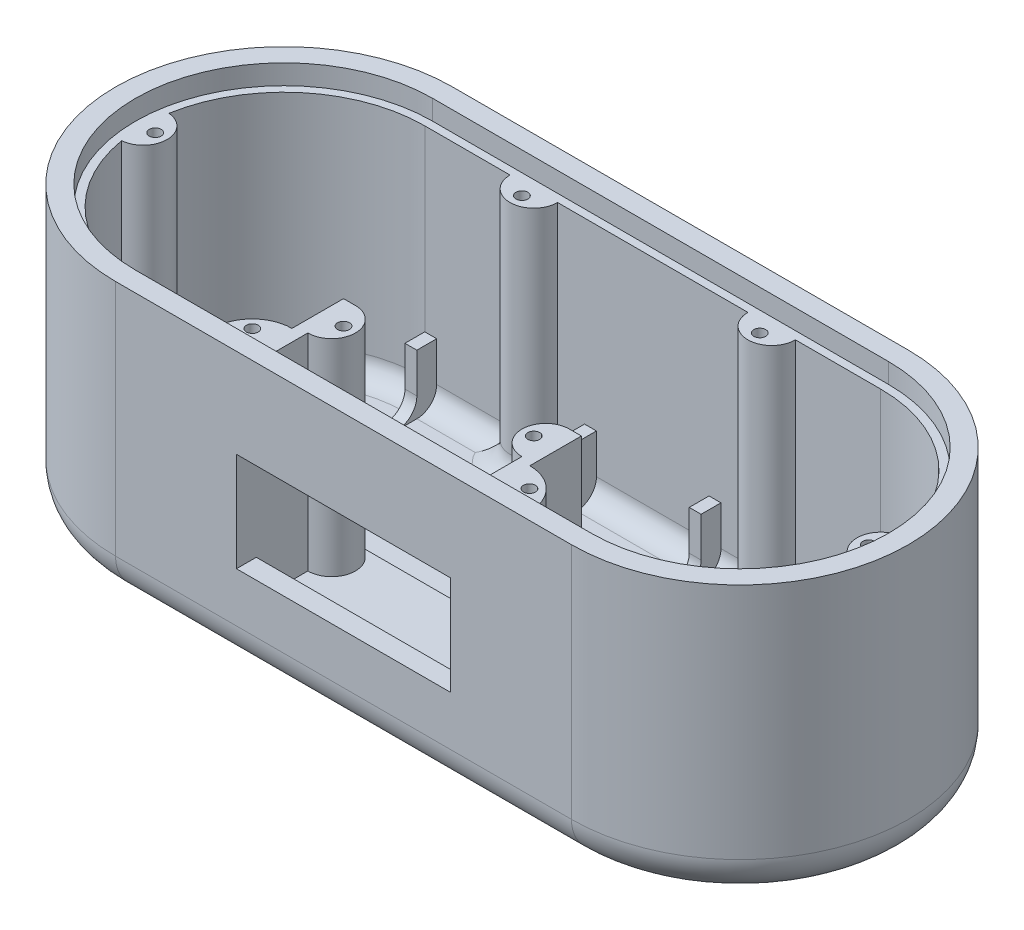
SolidWorks part; units mm, degrees
ref_plane "Front Plane" through (0, 0, 0) normal (0, 0, 1) x (1, 0, 0)
ref_plane "Top Plane" through (0, 0, 0) normal (0, 1, 0) x (1, 0, 0)
ref_plane "Right Plane" through (0, 0, 0) normal (1, 0, 0) x (0, 0, -1)
sketch "Sketch1" plane through (0, 0, 0) normal (0, 1, 0) x (1, 0, 0)
  line L0 (-57.5, 0) -> (57.5, 0) construction
  line L1 (-57.5, 42.5) -> (57.5, 42.5)
  line L2 (-57.5, -42.5) -> (57.5, -42.5)
  line L3 (-57.5, 0) -> (-100, 0) construction
  line L4 (57.5, 0) -> (100, 0) construction
  arc A0 (-57.5, 42.5) -> (-57.5, -42.5) centre (-57.5, 0) ccw
  arc A1 (57.5, -42.5) -> (57.5, 42.5) centre (57.5, 0) ccw
  point P3 (0, 0)
  point P12 (31.5337, 0)
  point P13 (0, 0)
  dimension "D1" = 85
  dimension "D2" = 200
extrude "Boss-Extrude1" add sketch "Sketch1" along normal blind 70
fillet "Fillet1" radius 10 4 edges at (0, 0, 42.5) (100, 0, 0) (0, 0, -42.5) (-100, 0, 0)
sketch "Sketch2" plane through (0, 70, 0) normal (0, 1, 0) x (1, 0, 0)
  line L2 (-57.5, -37.5) -> (-30, -37.5)
  line L3 (-30, -37.5) -> (-30, -12.5)
  line L4 (-57.5, -37.5) -> (57.5, -37.5)
  line L5 (57.5, 37.5) -> (-57.5, 37.5)
  line L7 (57.5, 37.5) -> (-57.5, 37.5)
  line L8 (-30, -12.5) -> (30, -12.5)
  line L9 (30, -12.5) -> (30, -37.5)
  line L10 (30, -37.5) -> (57.5, -37.5)
  line L11 (0, -12.5) -> (0, 0) construction
  arc A4 (-57.5, 37.5) -> (-57.5, -37.5) centre (-57.5, 0) ccw
  arc A5 (57.5, -37.5) -> (57.5, 37.5) centre (57.5, 0) ccw
  arc A6 (-57.5, 37.5) -> (-57.5, -37.5) centre (-57.5, 0) ccw
  arc A7 (57.5, -37.5) -> (57.5, 37.5) centre (57.5, 0) ccw
  dimension "D2" = 25
  dimension "D3" = 60
  dimension "D1" = 5
extrude "Cut-Extrude1" cut sketch "Sketch2" against normal blind 5
sketch "Sketch3" plane through (0, 65, 0) normal (0, 1, 0) x (1, 0, 0)
  line L0 (30, -12.5) -> (30, -37.5) construction
  line L1 (-30, -37.5) -> (-30, -12.5) construction
  line L2 (-30, -25.5) -> (30, -25.5) construction
  line L3 (-40, -35.5) -> (-30, -35.5) construction
  line L4 (40, -35.5) -> (30, -35.5) construction
  line L5 (-37.0711, -28.4289) -> (-30, -35.5) construction
  line L6 (-30, -37.5) -> (-30, -12.5) construction
  line L7 (30, -35.5) -> (37.0711, -28.4289) construction
  line L8 (-30, 32.5) -> (-30, 35.5) construction
  line L9 (30, 35.5) -> (30, 32.5) construction
  line L10 (-36, 35.5) -> (-57.5, 35.5)
  line L11 (24, 35.5) -> (-24, 35.5)
  line L12 (32, -35.5) -> (57.5, -35.5)
  line L13 (57.5, 35.5) -> (-57.5, 35.5)
  line L14 (-57.5, -35.5) -> (-32, -35.5)
  line L15 (-32, -35.5) -> (-32, -10.5)
  line L16 (-32, -10.5) -> (32, -10.5)
  line L17 (32, -10.5) -> (32, -35.5)
  line L18 (40, -35.5) -> (57.5, -35.5)
  line L19 (57.5, 35.5) -> (36, 35.5)
  line L20 (-57.5, -35.5) -> (-40, -35.5)
  line L21 (93, 0) -> (95, 0) construction
  line L24 (-93, 0) -> (-95, 0) construction
  line L25 (-34.9497, -30.5503) -> (34.9497, -30.5503) construction
  line L26 (-90, 0) -> (-87, 0) construction
  line L27 (90, 0) -> (87, 0) construction
  line L28 (30, 32.5) -> (30, 29.5) construction
  line L29 (-30, 32.5) -> (-30, 29.5) construction
  line L30 (-30, 29.5) -> (-30, -12.5) construction
  line L31 (30, 29.5) -> (30, -12.5) construction
  line L32 (-30, -25.5) -> (-30, -12.5)
  line L33 (-30, -12.5) -> (30, -12.5)
  line L34 (30, -12.5) -> (30, -25.5)
  arc A0 (40, -35.5) -> (30, -25.5) centre (30, -35.5) ccw
  arc A1 (-92.493, 5.9785) -> (-92.493, -5.9785) centre (-93, 0) cw
  arc A2 (-30, -25.5) -> (-40, -35.5) centre (-30, -35.5) ccw
  arc A3 (92.493, 5.9785) -> (92.493, -5.9785) centre (93, 0) ccw
  arc A4 (57.5, -35.5) -> (57.5, 35.5) centre (57.5, 0) ccw
  arc A5 (-57.5, 35.5) -> (-57.5, -35.5) centre (-57.5, 0) ccw
  arc A6 (57.5, -35.5) -> (92.493, -5.9785) centre (57.5, 0) ccw
  arc A7 (-57.5, 35.5) -> (-92.493, 5.9785) centre (-57.5, 0) ccw
  arc A8 (24, 35.5) -> (36, 35.5) centre (30, 35.5) ccw
  arc A9 (-36, 35.5) -> (-24, 35.5) centre (-30, 35.5) ccw
  arc A10 (-92.493, -5.9785) -> (-57.5, -35.5) centre (-57.5, 0) ccw
  arc A11 (92.493, 5.9785) -> (57.5, 35.5) centre (57.5, 0) ccw
  arc A12 (57.5, -37.5) -> (57.5, 37.5) centre (57.5, 0) ccw construction
  arc A13 (-57.5, 37.5) -> (-57.5, -37.5) centre (-57.5, 0) ccw construction
  arc A14 (-92.493, 5.9785) -> (-93, 0) centre (-57.5, 0) ccw construction
  arc A15 (-92.493, -5.9785) -> (-93, 0) centre (-57.5, 0) cw construction
  arc A16 (92.493, 5.9785) -> (93, 0) centre (57.5, 0) cw construction
  arc A17 (92.493, -5.9785) -> (93, 0) centre (57.5, 0) ccw construction
  circle A18 centre (-90, 0) radius 1.5
  circle A19 centre (-30, 32.5) radius 1.5
  circle A20 centre (30, 32.5) radius 1.5
  circle A21 centre (90, 0) radius 1.5
  circle A22 centre (34.9497, -30.5503) radius 1.5
  circle A23 centre (-34.9497, -30.5503) radius 1.5
  dimension "D2" = 10
  dimension "D3" = 6
  dimension "D4" = 3
  dimension "D5" = 3
  dimension "D6" = 42
  dimension "D7" = 3
  dimension "D1" = 2
extrude "Cut-Extrude2" cut sketch "Sketch3" against normal offset from surface (60 mm away) 5 up to face at (0, 0, 0)
fillet "Fillet2" radius 5 18 edges at (-48.75, 5, 35.5) (-80.3912, 5, 27.1338) (-87, 5, 0) (-80.3912, 5, -27.1338) (-46.75, 5, -35.5) (-30, 5, -29.5) (0, 5, -35.5) (30, 5, -29.5) (46.75, 5, -35.5) (80.3912, 5, -27.1338) (87, 5, 0) (80.3912, 5, 27.1338) (48.75, 5, 35.5) (37.0711, 5, 28.4289) (30, 5, 19) (0, 5, 12.5) (-30, 5, 19) (-37.0711, 5, 28.4289)
sketch "Sketch4" plane through (0, 65, 0) normal (0, 1, 0) x (1, 0, 0)
  line L5 (-57.5, -30.5) -> (-44.1421, -30.5) construction
  line L10 (-57.5, -35.5) -> (-54.5, -35.5)
  line L11 (-57.5, -35.5) -> (-57.5, -30.5)
  line L12 (-57.5, -30.5) -> (-54.5, -30.5)
  line L13 (-54.5, -35.5) -> (-54.5, -30.5)
  line L14 (24, 35.5) -> (-24, 35.5) construction
  line L15 (-17.202, 35.5) -> (-14.202, 35.5)
  line L16 (-17.202, 35.5) -> (-17.202, 30.5)
  line L17 (-17.202, 30.5) -> (-14.202, 30.5)
  line L18 (-14.202, 35.5) -> (-14.202, 30.5)
  line L19 (20.202, 30.5) -> (-20.202, 30.5) construction
  line L20 (-39.798, 30.5) -> (-57.5, 30.5) construction
  line L21 (17.202, 35.5) -> (14.202, 35.5)
  line L22 (17.202, 35.5) -> (17.202, 30.5)
  line L23 (17.202, 30.5) -> (14.202, 30.5)
  line L24 (14.202, 35.5) -> (14.202, 30.5)
  line L25 (-57.5, 35.5) -> (-54.5, 35.5)
  line L26 (-57.5, 35.5) -> (-57.5, 30.5)
  line L27 (-57.5, 30.5) -> (-54.5, 30.5)
  line L28 (-54.5, 35.5) -> (-54.5, 30.5)
  line L29 (57.5, 30.5) -> (39.798, 30.5) construction
  line L30 (57.5, 35.5) -> (54.5, 35.5)
  line L31 (57.5, 35.5) -> (57.5, 30.5)
  line L32 (57.5, 30.5) -> (54.5, 30.5)
  line L33 (54.5, 35.5) -> (54.5, 30.5)
  line L34 (44.1421, -30.5) -> (57.5, -30.5) construction
  line L35 (57.5, -35.5) -> (54.5, -35.5)
  line L36 (57.5, -35.5) -> (57.5, -30.5)
  line L37 (57.5, -30.5) -> (54.5, -30.5)
  line L38 (54.5, -35.5) -> (54.5, -30.5)
  dimension "D1" = 3
  dimension "D2" = 3
  dimension "D3" = 3
extrude "Boss-Extrude2" add sketch "Sketch4" against normal up to surface (60 mm away) up to face at (0, 5, 0.3691)
sketch "Sketch5" plane through (0, 65, 0) normal (0, 1, 0) x (1, 0, 0)
  line L1 (-57.5, 30.5) -> (-54.5, 30.5)
  line L2 (-57.5, 30.5) -> (-57.5, 35.5)
  line L3 (-57.5, 35.5) -> (-54.5, 35.5)
  line L4 (-54.5, 30.5) -> (-54.5, 35.5)
  line L5 (-17.202, 30.5) -> (-14.202, 30.5)
  line L6 (-17.202, 30.5) -> (-17.202, 35.5)
  line L7 (-17.202, 35.5) -> (-14.202, 35.5)
  line L8 (-14.202, 30.5) -> (-14.202, 35.5)
  line L9 (14.202, 30.5) -> (17.202, 30.5)
  line L10 (14.202, 30.5) -> (14.202, 35.5)
  line L11 (14.202, 35.5) -> (17.202, 35.5)
  line L12 (17.202, 30.5) -> (17.202, 35.5)
  line L13 (54.5, 30.5) -> (57.5, 30.5)
  line L14 (54.5, 30.5) -> (54.5, 35.5)
  line L15 (54.5, 35.5) -> (57.5, 35.5)
  line L16 (57.5, 30.5) -> (57.5, 35.5)
  line L17 (54.5, -30.5) -> (57.5, -30.5)
  line L18 (54.5, -30.5) -> (54.5, -35.5)
  line L19 (54.5, -35.5) -> (57.5, -35.5)
  line L20 (57.5, -30.5) -> (57.5, -35.5)
  line L21 (-57.5, -30.5) -> (-54.5, -30.5)
  line L22 (-57.5, -30.5) -> (-57.5, -35.5)
  line L23 (-57.5, -35.5) -> (-54.5, -35.5)
  line L24 (-54.5, -30.5) -> (-54.5, -35.5)
extrude "Cut-Extrude3" cut sketch "Sketch5" against normal offset from surface (45 mm away) 15 up to face at (0, 5, -4.4367)
fillet "Fillet3" radius 5 6 edges at (15.702, 5, -30.5) (-56, 5, 30.5) (56, 5, 30.5) (56, 5, -30.5) (-15.702, 5, -30.5) (-56, 5, -30.5)
sketch "Sketch6" plane through (0, 5, 0) normal (0, 1, 0) x (1, 0, 0)
  circle A0 centre (-57.5, 0) radius 3
  circle A1 centre (-57.5, 0) radius 1.5
  circle A2 centre (57.5, 0) radius 3
  circle A3 centre (57.5, 0) radius 1.5
  arc A4 (-57.5, 30.5) -> (-86.6479, 8.9806) centre (-57.5, 0) ccw construction
  arc A5 (86.6479, 8.9806) -> (57.5, 30.5) centre (57.5, 0) ccw construction
  dimension "D1" = 3
  dimension "D2" = 6
extrude "Boss-Extrude3" add sketch "Sketch6" along normal up to surface (15 mm away) up to face at (-56, 20, -33)
fillet "Fillet4" radius 1 2 edges at (57.5, 5, 3) (-57.5, 5, 3)
sketch "Sketch8" plane through (0, 0, 12.5) normal (0, 0, -1) x (-1, 0, 0)
  line L5 (-57.5, 70) -> (57.5, 70) construction
  line L6 (-30, 70) -> (30, 70)
  line L8 (-27, 67) -> (-27, 13)
  line L9 (-27, 13) -> (27, 13)
  line L10 (27, 13) -> (27, 67)
  line L11 (27, 67) -> (-27, 67)
  line L12 (-27, 67) -> (-27, 13)
  line L13 (-27, 13) -> (27, 13)
  line L14 (27, 13) -> (27, 67)
  line L16 (30, 70) -> (-30, 70) construction
  line L17 (27, 67) -> (30, 67)
  line L18 (30, 10) -> (30, 70) construction
  line L19 (30, 67) -> (30, 70)
  line L20 (-27, 67) -> (-30, 67)
  line L21 (-30, 10) -> (-30, 70) construction
  line L22 (-30, 67) -> (-30, 70)
  dimension "D1" = 3
extrude "Cut-Extrude4" cut sketch "Sketch8" against normal offset from surface (25 mm away) 5 up to face at (0, 40, 42.5)
sketch "Sketch10" plane through (0, 0, 37.5) normal (0, 0, -1) x (-1, 0, 0)
  line L0 (27, 67) -> (27, 13) construction
  line L1 (-26.99, 47.5) -> (27, 47.5)
  line L2 (-26.99, 47.5) -> (-26.99, 22.5)
  line L3 (-26.99, 22.5) -> (27, 22.5)
  line L4 (27, 47.5) -> (27, 22.5)
  line L5 (-26.99, 47.5) -> (-26.99, 70) construction
  line L6 (-57.5, 70) -> (57.5, 70) construction
  line L7 (-26.99, 22.5) -> (-26.99, 0) construction
  line L8 (57.5, 0) -> (-57.5, 0) construction
  dimension "D1" = 25
extrude "Cut-Extrude5" cut sketch "Sketch10" against normal blind 5
sketch "Sketch12" plane through (0, 13, 0) normal (0, 1, 0) x (1, 0, 0)
  line L0 (27, -37.5) -> (27, -12.5) construction
  line L1 (-27, -37.5) -> (-27, -12.5) construction
  line L2 (30, -12.5) -> (-30, -12.5) construction
  line L3 (-27, -37.5) -> (-27, -12.5) construction
  line L4 (-21, -18.5) -> (-24, -18.5) construction
  line L5 (21, -18.5) -> (24, -18.5) construction
  line L7 (-27, -24.5) -> (-27, -12.5)
  line L8 (27, -24.5) -> (27, -12.5)
  arc A0 (27, -12.5) -> (27, -24.5) centre (27, -18.5) ccw
  arc A1 (-27, -12.5) -> (-27, -24.5) centre (-27, -18.5) cw
  circle A2 centre (-24, -18.5) radius 1.5
  circle A3 centre (24, -18.5) radius 1.5
  dimension "D1" = 6
  dimension "D3" = 3
  dimension "D2" = 3
extrude "Boss-Extrude5" add sketch "Sketch12" along normal up to surface (54 mm away) up to face at (28.5, 67, 25)
sketch "Sketch13" plane through (0, 67, 0) normal (0, 1, 0) x (1, 0, 0)
  line L12 (-30, -37.5) -> (-27, -37.5)
  line L13 (-27, -37.5) -> (-27, -24.5)
  line L14 (-27, -12.5) -> (-30, -12.5)
  line L15 (-30, -12.5) -> (-30, -37.5)
  line L16 (-30, -37.5) -> (-27, -37.5)
  line L17 (-27, -37.5) -> (-27, -24.5)
  line L18 (-27, -12.5) -> (-30, -12.5)
  line L19 (-30, -12.5) -> (-30, -37.5)
  line L24 (27, -37.5) -> (30, -37.5)
  line L25 (30, -37.5) -> (30, -12.5)
  line L26 (30, -12.5) -> (27, -12.5)
  line L27 (27, -24.5) -> (27, -37.5)
  line L28 (27, -37.5) -> (30, -37.5)
  line L29 (30, -37.5) -> (30, -12.5)
  line L30 (30, -12.5) -> (27, -12.5)
  line L31 (27, -24.5) -> (27, -37.5)
  arc A3 (-27, -24.5) -> (-27, -12.5) centre (-27, -18.5) ccw
  arc A4 (-27, -24.5) -> (-27, -12.5) centre (-27, -18.5) ccw
  arc A6 (27, -12.5) -> (27, -24.5) centre (27, -18.5) ccw
  arc A7 (27, -12.5) -> (27, -24.5) centre (27, -18.5) ccw
  dimension "D1" = 0
  dimension "D2" = 0
extrude "Cut-Extrude6" cut sketch "Sketch13" against normal up to surface (2 mm away) up to face at (0, 65, 2.8572)
